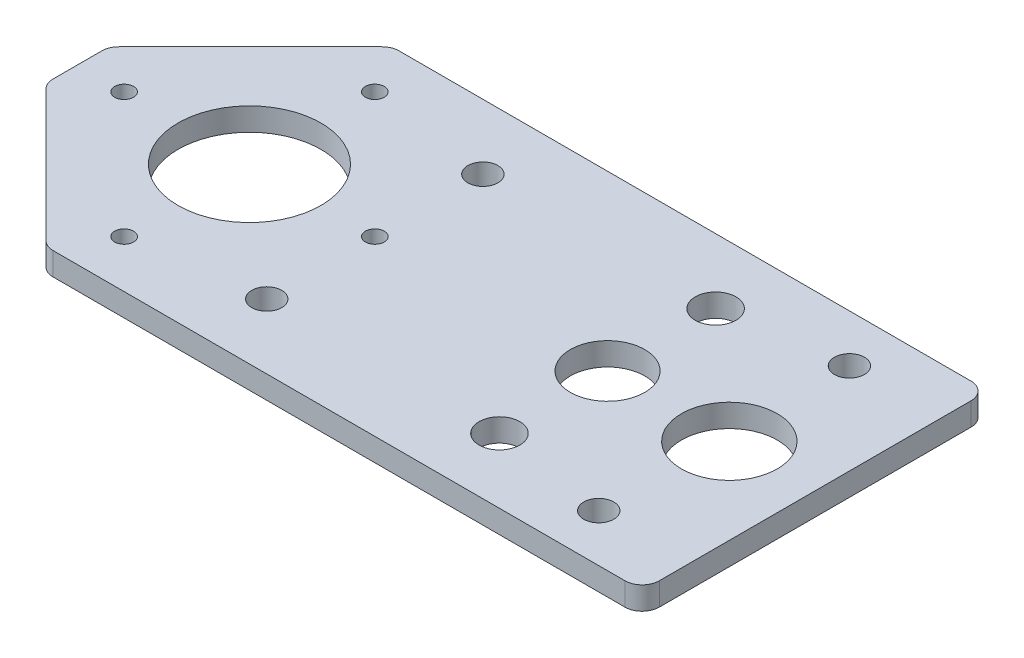
SolidWorks part; units mm, degrees
ref_plane "Front Plane" through (0, 0, 0) normal (0, 0, 1) x (1, 0, 0)
ref_plane "Top Plane" through (0, 0, 0) normal (0, 1, 0) x (1, 0, 0)
ref_plane "Right Plane" through (0, 0, 0) normal (1, 0, 0) x (0, 0, -1)
ref_plane "Plane1" through (0, 0, 0) normal (0, -1, 0) x (1, 0, 0)
sketch "Sketch1" plane through (0, 0, 0) normal (0, -1, 0) x (1, 0, 0)
  line L0 (0, -27.25) -> (0, 27.25)
  line L1 (-3, 30.25) -> (-103.0089, 30.25)
  line L2 (-105.1303, 29.3713) -> (-128.1213, 6.3803)
  line L3 (-129, 4.2589) -> (-129, -4.2589)
  line L4 (-128.1213, -6.3803) -> (-105.1303, -29.3713)
  line L5 (-103.0089, -30.25) -> (-3, -30.25)
  line L6 (-120.8406, 0) -> (-98.9203, -21.9203) construction
  line L7 (-120.8406, 0) -> (-98.9203, 21.9203) construction
  line L8 (-98.9203, 21.9203) -> (-77, 0) construction
  line L9 (-77, 0) -> (-98.9203, -21.9203) construction
  line L10 (-120.8406, 0) -> (-77, 0) construction
  line L11 (-77, 18.9) -> (-77, -18.9) construction
  line L12 (-15.9201, 21.9203) -> (-15.9201, -21.9203) construction
  line L13 (-36.3, 18.9) -> (-36.3, -18.9) construction
  line L14 (-98.9203, 21.9203) -> (-98.9203, -21.9203) construction
  circle A0 centre (-15, 0) radius 8.375
  circle A1 centre (-36.3, 18.9) radius 3.56
  circle A2 centre (-77, 18.9) radius 2.625
  circle A3 centre (-36.3, -18.9) radius 3.56
  circle A4 centre (-77, -18.9) radius 2.625
  circle A5 centre (-98.9203, 0) radius 12.5
  circle A6 centre (-77, 0) radius 1.65
  circle A7 centre (-120.8406, 0) radius 1.65
  circle A8 centre (-98.9203, -21.9203) radius 1.65
  circle A9 centre (-98.9203, 21.9203) radius 1.65
  circle A10 centre (-15.9201, 21.9203) radius 2.625
  circle A11 centre (-15.9201, -21.9203) radius 2.625
  circle A12 centre (-36.3, 0) radius 6.5
  arc A13 (-3, -30.25) -> (0, -27.25) centre (-3, -27.25) ccw
  arc A14 (0, 27.25) -> (-3, 30.25) centre (-3, 27.25) ccw
  arc A15 (-103.0089, 30.25) -> (-105.1303, 29.3713) centre (-103.0089, 27.25) ccw
  arc A16 (-128.1213, 6.3803) -> (-129, 4.2589) centre (-126, 4.2589) ccw
  arc A17 (-129, -4.2589) -> (-128.1213, -6.3803) centre (-126, -4.2589) ccw
  arc A18 (-105.1303, -29.3713) -> (-103.0089, -30.25) centre (-103.0089, -27.25) ccw
  point P46 (-98.9203, 0)
  dimension "D3" = 3
  dimension "D4" = 3
  dimension "D9" = 16.75
  dimension "D10" = 3.3
  dimension "D11" = 7.12
  dimension "D12" = 5.25
  dimension "D13" = 25
  dimension "D14" = 13
  dimension "D1" = 60.5
  dimension "D2" = 129
  dimension "D5" = 45
  dimension "D6" = 15
  dimension "D7" = 36.3
  dimension "D8" = 40.7
  dimension "D15" = 31
  dimension "D16" = 31
  dimension "D17" = 1.8402
  dimension "D18" = 30.25
  dimension "D19" = 43.8406
  dimension "D20" = 37.8
  dimension "D21" = 11.35
  dimension "D22" = 45
  dimension "D23" = 100.0089
  dimension "D24" = 21.9203
extrude "Boss-Extrude1" add sketch "Sketch1" against normal blind 4
